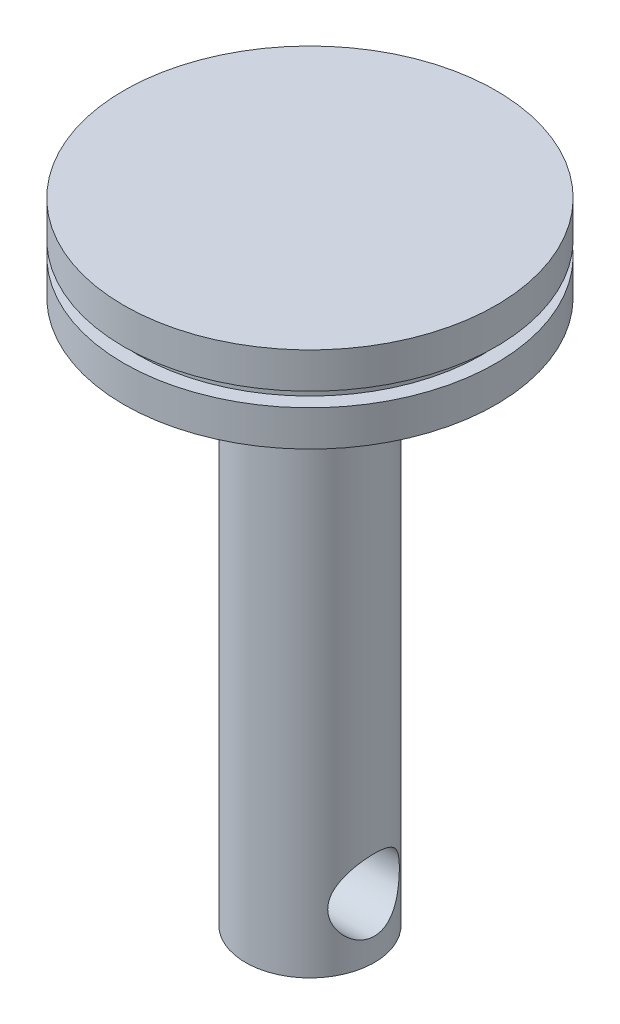
SolidWorks part; units mm, degrees
ref_plane "Front Plane" through (0, 0, 0) normal (0, 0, 1) x (1, 0, 0)
ref_plane "Top Plane" through (0, 0, 0) normal (0, 1, 0) x (1, 0, 0)
ref_plane "Right Plane" through (0, 0, 0) normal (1, 0, 0) x (0, 0, -1)
sketch "Sketch1" plane through (0, 0, 0) normal (0, 0, 1) x (1, 0, 0)
  line L0 (0, 49.3119) -> (0, -54.2267) construction
  line L1 (0, 2.076) -> (13, 2.076)
  line L3 (13, -3.924) -> (0, -3.924)
  line L4 (13, 2.076) -> (13, -0.424)
  line L6 (13, -1.424) -> (12, -1.424)
  line L7 (12, -1.424) -> (12, -0.424)
  line L8 (12, -0.424) -> (13, -0.424)
  line L9 (0, 2.076) -> (0, -3.924)
  line L10 (13, -1.424) -> (13, -3.924)
revolve "Revolve1" add sketch "Sketch1" angle 360 about L0
sketch "Sketch2" plane through (0, -3.924, 0) normal (0, -1, 0) x (1, 0, 0)
  circle A0 centre (0, 0) radius 4.5
extrude "Boss-Extrude1" add sketch "Sketch2" along normal blind 30
sketch "Sketch3" plane through (0, 0, 0) normal (1, 0, 0) x (0, 0, -1)
  line L0 (-4.5, -33.924) -> (4.5, -33.924)
  line L1 (0, -33.924) -> (0, -37.824)
  circle A2 centre (0, -37.824) radius 5.9548
extrude "Boss-Extrude2" add sketch "Sketch3" along normal blind 1 and the other way blind 1 contours L0 A2 region at (0, -38.4403, 0)
sketch "Sketch5" plane through (1, 0, 0) normal (1, 0, 0) x (0, 0, -1)
  line L0 (-5.2055, -40.7159) -> (5.2055, -40.7159)
  arc A0 (-4.5, -33.924) -> (4.5, -33.924) centre (0, -37.824) ccw construction
  arc M4 (-4.5, -33.924) -> (4.5, -33.924) centre (0, -37.824) ccw
extrude "Cut-Extrude3" cut sketch "Sketch5" against normal through all contours L0 M4 region at (1, -41.9729, 0)
sketch "Sketch6" plane through (0, -33.924, 0) normal (0, -1, 0) x (1, 0, 0)
  circle A0 centre (0, 0) radius 4.5
  arc A1 (1, -4.3875) -> (1, 4.3875) centre (0, 0) ccw construction
extrude "Boss-Extrude3" add sketch "Sketch6" along normal blind 8
sketch "Sketch4" plane through (-1, 0, 0) normal (-1, 0, 0) x (0, 0, 1)
  circle A0 centre (0, -37.824) radius 2.5
extrude "Cut-Extrude2" cut sketch "Sketch4" against normal through all and the other way blind 8
sketch "Sketch7" plane through (0, -41.924, 0) normal (0, -1, 0) x (1, 0, 0)
  circle A0 centre (0, 0) radius 4.5 construction
  circle A1 centre (0, 0) radius 4.5
  circle A2 centre (0, 0) radius 6.9503
extrude "Cut-Extrude5" cut sketch "Sketch7" against normal blind 8
